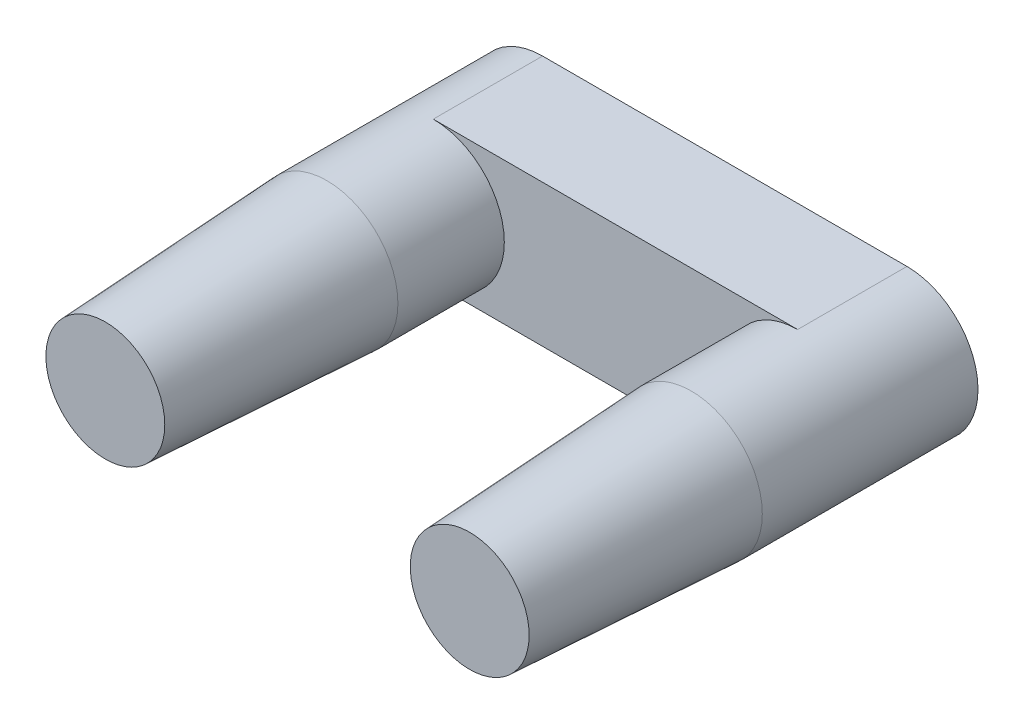
SolidWorks part; units mm, degrees
ref_plane "Front Plane" through (0, 0, 0) normal (0, 0, 1) x (1, 0, 0)
ref_plane "Top Plane" through (0, 0, 0) normal (0, 1, 0) x (1, 0, 0)
ref_plane "Right Plane" through (0, 0, 0) normal (1, 0, 0) x (0, 0, -1)
sketch "Sketch1" plane through (0, 0, 0) normal (0, 0, 1) x (1, 0, 0)
  line L0 (-10, 1.95) -> (0, 1.95)
  line L1 (-10, -1.95) -> (0, -1.95)
  circle A0 centre (0, 0) radius 1.95
  circle A1 centre (-10, 0) radius 1.95
  dimension "D2" = 3.9
  dimension "D1" = 10
extrude "Boss-Extrude1" add sketch "Sketch1" along normal blind 9 contours A1 | A0 region at (-10, 0, 0) region at (0, 0, 0)
extrude "Boss-Extrude2" add sketch "Sketch1<3>" against normal blind 3 contours A1 L1 A0 L0 | A1 | A0 region at (-5, 0, 0) region at (-10, 0, 0) region at (0, 0, 0)
sketch "Sketch1<3>" plane through (0, 0, 0) normal (0, 0, 1) x (1, 0, 0) same geometry as "Sketch1"
chamfer "Chamfer1" distance 6.08 angle 3 2 edges at (1.95, 0, 9) (-8.05, 0, 9) first distance on face at (0, 0, -1.5) first distance on face at (-8.05, 0, 9)
